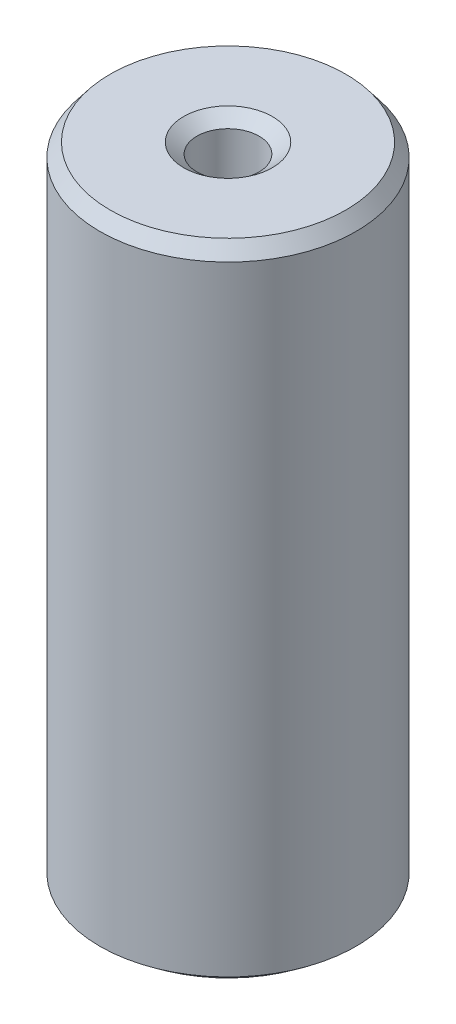
SolidWorks part; units mm, degrees
ref_plane "Front Plane" through (0, 0, 0) normal (0, 0, 1) x (1, 0, 0)
ref_plane "Top Plane" through (0, 0, 0) normal (0, 1, 0) x (1, 0, 0)
ref_plane "Right Plane" through (0, 0, 0) normal (1, 0, 0) x (0, 0, -1)
sketch "Sketch1" plane through (0, 0, 0) normal (0, 1, 0) x (1, 0, 0)
  circle A0 centre (0, 0) radius 5
  dimension "SLEEVE_OD" = 10
extrude "Boss-Extrude1" add sketch "Sketch1" along normal blind 25.0853
sketch "Sketch2" plane through (0, 0, 0) normal (0, 1, 0) x (1, 0, 0)
  circle A0 centre (0, 0) radius 1.212
  dimension "BORE_D" = 2.4239
extrude "Cut-Extrude1" cut sketch "Sketch2" along normal through all
chamfer "Chamfer1" distance 0.5202 angle 37.734 4 edges at (0, 25.0853, 1.212) (0, 0, 1.212) (0, 0, 5) (0, 25.0853, 5) first distance on face at (0, 25.0853, 1.212) first distance on face at (0, 0, 1.212) first distance on face at (0, 25.0853, 5)
